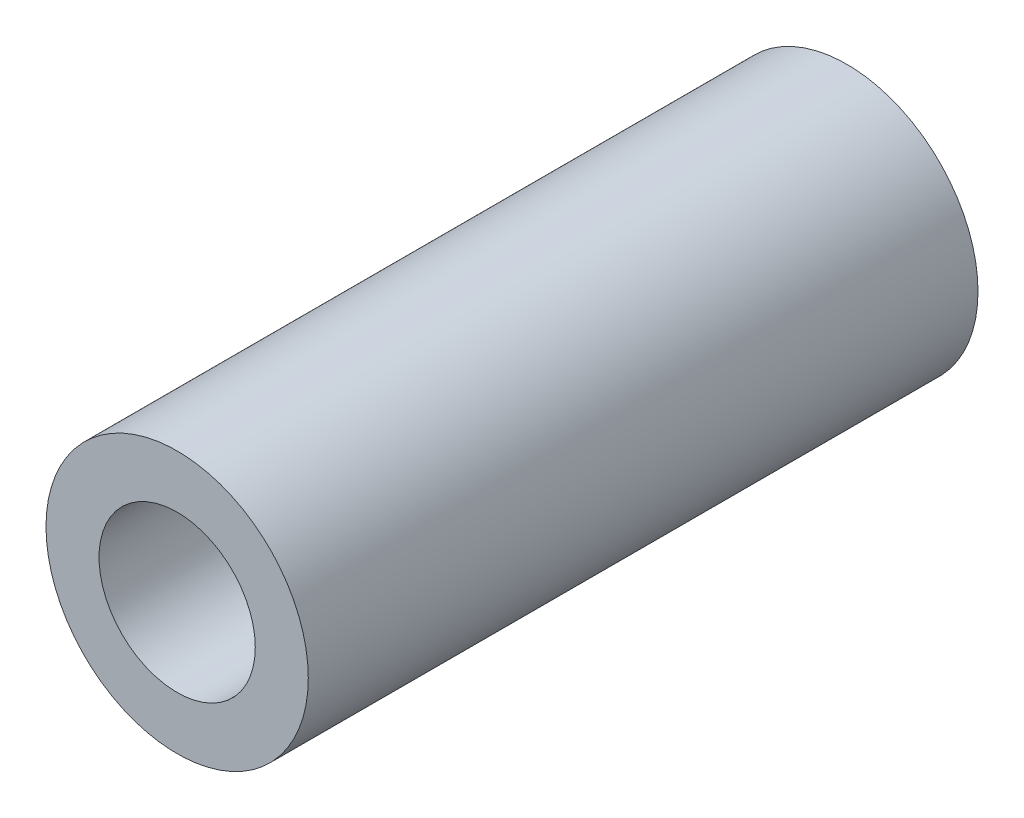
SolidWorks part; units mm, degrees
ref_plane "Front Plane" through (0, 0, 0) normal (0, 0, 1) x (1, 0, 0)
ref_plane "Top Plane" through (0, 0, 0) normal (0, 1, 0) x (1, 0, 0)
ref_plane "Right Plane" through (0, 0, 0) normal (1, 0, 0) x (0, 0, -1)
other "Configuration Table"
sketch "Sketch1" plane through (0, 0, 0) normal (0, 0, 1) x (1, 0, 0)
  circle A0 centre (0, 0) radius 11.75
  circle A1 centre (0, 0) radius 7
extrude "Pin" add sketch "Sketch1" along normal mid plane 60
ref_axis "Pin Axis" through (0, 0, -199.0801) along (0, 0, 1)
